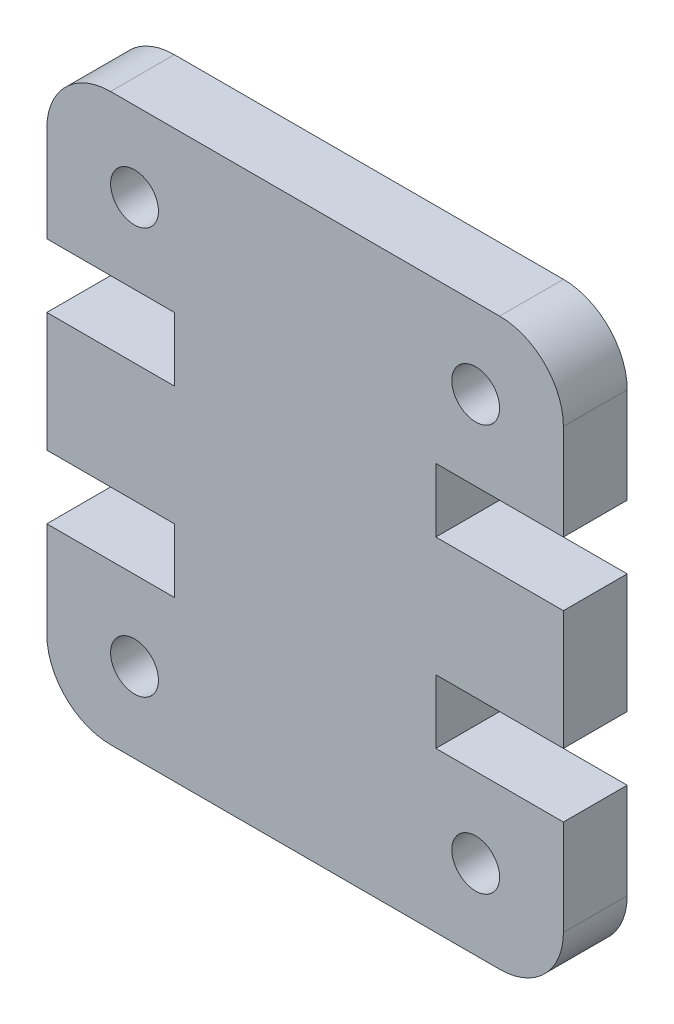
SolidWorks part; units mm, degrees
ref_plane "Front Plane" through (0, 0, 0) normal (0, 0, 1) x (1, 0, 0)
ref_plane "Top Plane" through (0, 0, 0) normal (0, 1, 0) x (1, 0, 0)
ref_plane "Right Plane" through (0, 0, 0) normal (1, 0, 0) x (0, 0, -1)
sketch "Sketch1" plane through (0, 0, 0) normal (0, 0, 1) x (1, 0, 0)
  line L0 (0, 10.74) -> (0, 7)
  line L1 (16.2, 10.74) -> (16.2, 7)
  line L2 (2, 17.74) -> (14.2, 17.74)
  line L3 (2, 0) -> (14.2, 0)
  line L4 (4, 12.74) -> (4, 10.74)
  line L5 (0, 12.74) -> (4, 12.74)
  line L6 (4, 10.74) -> (0, 10.74)
  line L7 (4, 7) -> (4, 5)
  line L8 (0, 15.74) -> (0, 12.74)
  line L9 (16.2, 12.74) -> (16.2, 15.74)
  line L10 (0, 7) -> (4, 7)
  line L11 (12.2, 12.74) -> (12.2, 10.74)
  line L12 (4, 5) -> (0, 5)
  line L13 (12.2, 10.74) -> (16.2, 10.74)
  line L14 (16.2, 12.74) -> (12.2, 12.74)
  line L15 (12.2, 7) -> (12.2, 5)
  line L16 (0, 2) -> (0, 5)
  line L17 (16.2, 5) -> (16.2, 2)
  line L18 (12.2, 5) -> (16.2, 5)
  line L19 (16.2, 7) -> (12.2, 7)
  arc A0 (16.2, 15.74) -> (14.2, 17.74) centre (14.2, 15.74) ccw
  arc A1 (2, 17.74) -> (0, 15.74) centre (2, 15.74) ccw
  arc A2 (14.2, 0) -> (16.2, 2) centre (14.2, 2) ccw
  arc A3 (0, 2) -> (2, 0) centre (2, 2) ccw
  circle A4 centre (13.45, 2.5) radius 0.75
  circle A5 centre (2.75, 2.5) radius 0.75
  circle A6 centre (13.45, 15.24) radius 0.75
  circle A7 centre (2.75, 15.24) radius 0.75
extrude "Boss-Extrude1" add sketch "Sketch1" along normal blind 2
